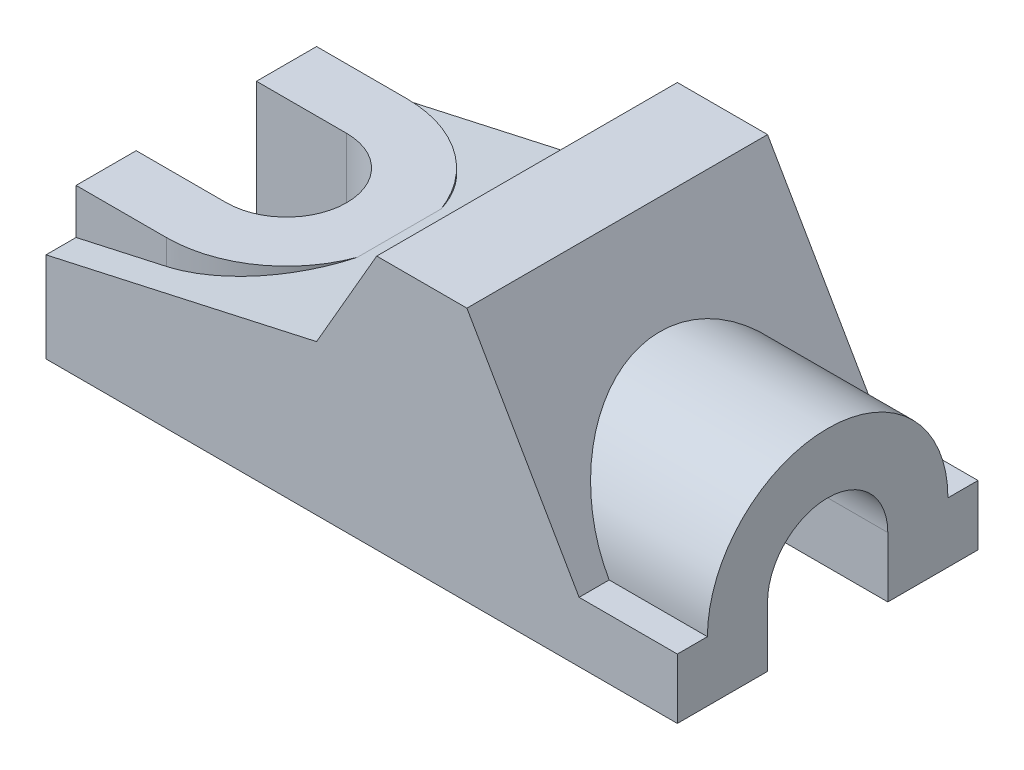
SolidWorks part; units mm, degrees
ref_plane "Front Plane" through (0, 0, 0) normal (0, 0, 1) x (1, 0, 0)
ref_plane "Top Plane" through (0, 0, 0) normal (0, 1, 0) x (1, 0, 0)
ref_plane "Right Plane" through (0, 0, 0) normal (1, 0, 0) x (0, 0, -1)
sketch "Sketch1" plane through (0, 0, 0) normal (0, 0, 1) x (1, 0, 0)
  line L0 (0, 0) -> (133.35, 0)
  line L1 (0, 0) -> (0, 19.05)
  line L2 (0, 19.05) -> (57.15, 31.75)
  line L3 (57.15, 31.75) -> (69.85, 53.747)
  line L4 (69.85, 53.747) -> (88.9, 53.747)
  line L5 (88.9, 53.747) -> (112.5985, 12.7)
  line L6 (112.5985, 12.7) -> (133.35, 12.7)
  line L7 (133.35, 12.7) -> (133.35, 0)
  dimension "D1" = 133.35
  dimension "D2" = 19.05
  dimension "D3" = 57.15
  dimension "D4" = 31.75
  dimension "D5" = 12.7
  dimension "D6" = 44.45
  dimension "D7" = 19.05
  dimension "D8" = 30
  dimension "D9" = 30
extrude "Boss-Extrude1" add sketch "Sketch1" along normal mid plane 63.5
sketch "Sketch2" plane through (133.35, 0, 0) normal (1, 0, 0) x (0, 0, -1)
  line L0 (0, 0) -> (0, 12.7) construction
  line L1 (-25.4, 12.7) -> (-25.4, 0)
  line L2 (-31.75, 0) -> (31.75, 0) construction
  line L3 (-25.4, 0) -> (25.4, 0)
  line L4 (25.4, 12.7) -> (25.4, 0)
  line L5 (-12.7, 12.7) -> (-12.7, 0)
  line L6 (12.7, 12.7) -> (12.7, 0)
  arc A0 (25.4, 12.7) -> (-25.4, 12.7) centre (0, 12.7) ccw
  arc A1 (12.7, 12.7) -> (-12.7, 12.7) centre (0, 12.7) ccw
  line M3 (31.75, 12.7) -> (-31.75, 12.7)
  line M5 (-31.75, 0) -> (31.75, 0)
  dimension "D2" = 50.8
  dimension "D3" = 25.4
  dimension "D1" = 12.7
extrude "Boss-Extrude2" add sketch "Sketch2" against normal up to surface (20.7515 mm away) contours A1 A0 M3 | L5 L1 M3 M5 | L6 L4 M3 M5 region at (133.35, 6.35, 19.05) region at (133.35, 37.532, 0) region at (133.35, 6.35, -19.05) up to face at (100.7493, 33.2235, 0)
extrude "Cut-Extrude1" cut sketch "Sketch2<3>" against normal blind 53.975 contours L3 L0 L5 M3 | L0 L6 M5 M3 | A1 M3 region at (133.35, 6.35, 6.35) region at (133.35, 6.35, -6.35) region at (133.35, 18.09, 0)
sketch "Sketch2<3>" plane through (133.35, 0, 0) normal (1, 0, 0) x (0, 0, -1) same geometry as "Sketch2"
ref_plane "Plane1" through (0, 28.575, 0) normal (0, -1, 0) x (-1, 0, 0)
sketch "Sketch4" plane through (0, 28.575, 0) normal (0, -1, 0) x (-1, 0, 0)
  line L0 (0, 0) -> (-19.05, 0) construction
  line L1 (0, -31.75) -> (0, 31.75) construction
  line L2 (-19.05, 12.7) -> (0, 12.7)
  line L3 (-19.05, 25.4) -> (0, 25.4)
  line L4 (0, 25.4) -> (0, 12.7)
  line L5 (-19.05, -12.7) -> (0, -12.7)
  line L6 (-19.05, -25.4) -> (0, -25.4)
  line L7 (0, -25.4) -> (0, -12.7)
  line L8 (0, 12.7) -> (0, -12.7)
  circle A0 centre (-19.05, 0) radius 12.7
  arc A1 (-19.05, 25.4) -> (-19.05, -25.4) centre (-19.05, 0) ccw
  dimension "D2" = 25.4
  dimension "D3" = 50.8
  dimension "D1" = 19.05
extrude "Boss-Extrude4" add sketch "Sketch4" along normal up to surface (9.525 mm away) contours L3 A1 L6 L7 L5 A0 L2 L4 region at (32.425, 28.575, 0) up to face at (28.575, 25.4, 0)
extrude "Cut-Extrude2" cut sketch "Sketch4<3>" along normal through all contours A0 | L0 L8 L2 A0 | L8 L0 A0 L5 region at (4.9804, 28.575, 7.4051) region at (4.9804, 28.575, -7.4051) region at (10.3237, 28.575, 8.7263)
sketch "Sketch4<3>" plane through (0, 28.575, 0) normal (0, -1, 0) x (-1, 0, 0) same geometry as "Sketch4"
